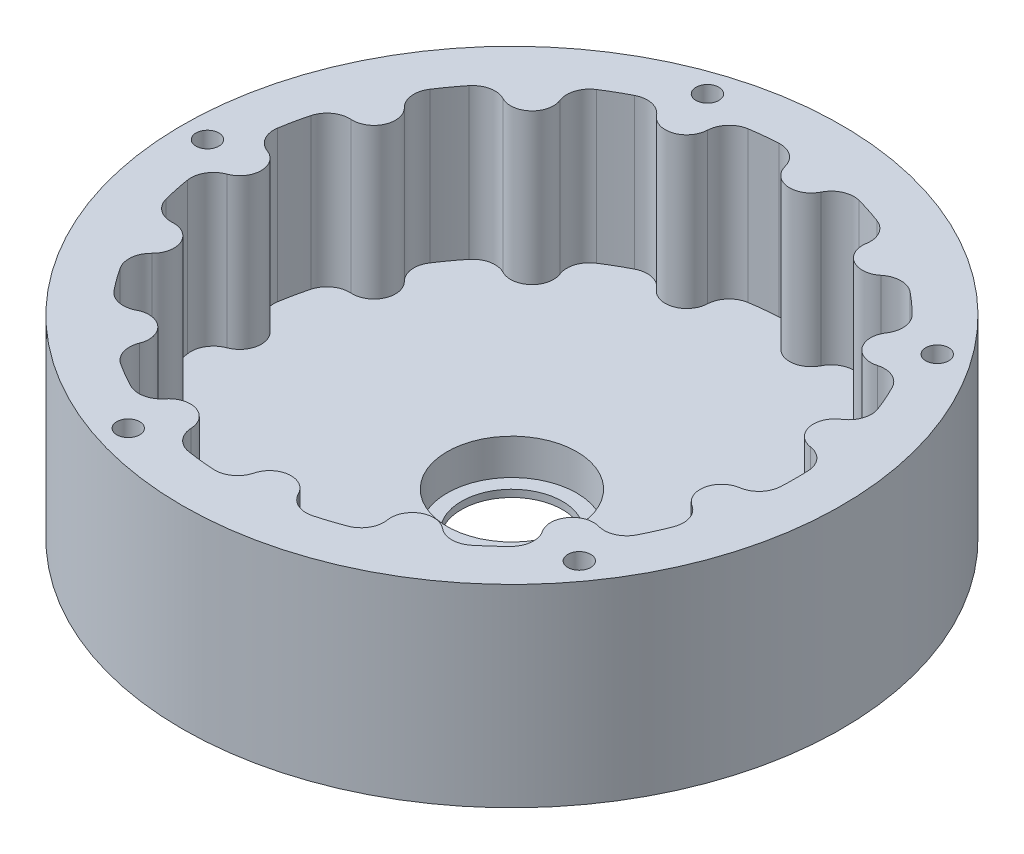
SolidWorks part; units mm, degrees
ref_plane "Front Plane" through (0, 0, 0) normal (0, 0, 1) x (1, 0, 0)
ref_plane "Top Plane" through (0, 0, 0) normal (0, 1, 0) x (1, 0, 0)
ref_plane "Right Plane" through (0, 0, 0) normal (1, 0, 0) x (0, 0, -1)
sketch "Sketch1" plane through (0, 0, 0) normal (0, 1, 0) x (1, 0, 0)
  line L0 (0, 0) -> (-38, 0) construction
  line L1 (-38.6368, 8.2125) -> (0, 0) construction
  circle A0 centre (0, 0) radius 46
  arc A1 (-36.9604, -2.8141) -> (-36.9604, 2.8141) centre (-38, 0) ccw
  arc A2 (-36.9604, 2.8141) -> (-38.9946, 6.2987) centre (-35.8602, 5.7924) cw
  arc A3 (-38.9946, 6.2987) -> (-38.6368, 8.2125) centre (0, 0) cw
  arc A4 (-38.9946, -6.2987) -> (-38.6368, -8.2125) centre (0, 0) ccw
  arc A5 (-36.9604, -2.8141) -> (-38.9946, -6.2987) centre (-35.8602, -5.7924) ccw
  arc A6 (-38.1852, 10.1064) -> (-38.6368, 8.2125) centre (0, 0) ccw
  arc A7 (-34.9096, 12.4623) -> (-38.1852, 10.1064) centre (-35.1159, 9.294) ccw
  arc A8 (-34.9096, 12.4623) -> (-32.6204, 17.604) centre (-34.7147, 15.456) ccw
  arc A9 (-32.6204, 17.604) -> (-33.0614, 21.6147) centre (-30.4039, 19.8773) cw
  arc A10 (-33.0614, 21.6147) -> (-31.9562, 23.2175) centre (0, 0) cw
  arc A11 (-30.7733, 24.764) -> (-31.9562, 23.2175) centre (0, 0) ccw
  arc A12 (-26.8226, 25.5839) -> (-30.7733, 24.764) centre (-28.2997, 22.7734) ccw
  arc A13 (-26.8226, 25.5839) -> (-22.64, 29.35) centre (-25.427, 28.2395) ccw
  arc A14 (-22.64, 29.35) -> (-21.4116, 33.1933) centre (-19.6906, 30.5252) cw
  arc A15 (-21.4116, 33.1933) -> (-19.75, 34.208) centre (0, 0) cw
  arc A16 (-18.0404, 35.1396) -> (-19.75, 34.208) centre (0, 0) ccw
  arc A17 (-14.0978, 34.2818) -> (-18.0404, 35.1396) centre (-16.5903, 32.3151) ccw
  arc A18 (-14.0978, 34.2818) -> (-8.745, 36.0211) centre (-11.7426, 36.1401) ccw
  arc A19 (-8.745, 36.0211) -> (-6.0596, 39.0324) centre (-5.5725, 35.895) cw
  arc A20 (-6.0596, 39.0324) -> (-4.1289, 39.2836) centre (0, 0) cw
  arc A21 (-2.1881, 39.4393) -> (-4.1289, 39.2836) centre (0, 0) ccw
  arc A22 (1.0647, 37.0521) -> (-2.1881, 39.4393) centre (-2.0123, 36.2692) ccw
  arc A23 (1.0647, 37.0521) -> (6.6621, 36.4638) centre (3.9721, 37.7918) ccw
  arc A24 (6.6621, 36.4638) -> (10.3402, 38.1226) centre (9.5091, 35.0583) cw
  arc A25 (10.3402, 38.1226) -> (12.2062, 37.5667) centre (0, 0) cw
  arc A26 (14.0425, 36.9196) -> (12.2062, 37.5667) centre (0, 0) ccw
  arc A27 (16.0431, 33.4157) -> (14.0425, 36.9196) centre (12.9137, 33.952) ccw
  arc A28 (16.0431, 33.4157) -> (20.9173, 30.6016) centre (19, 32.909) ccw
  arc A29 (20.9173, 30.6016) -> (24.9521, 30.6209) centre (22.9465, 28.1596) cw
  arc A30 (24.9521, 30.6209) -> (26.4307, 29.3542) centre (0, 0) cw
  arc A31 (27.845, 28.0162) -> (26.4307, 29.3542) centre (0, 0) ccw
  arc A32 (28.2475, 24.0015) -> (27.845, 28.0162) centre (25.6068, 25.7642) ccw
  arc A33 (28.2475, 24.0015) -> (31.5557, 19.4481) centre (30.7426, 22.3358) ccw
  arc A34 (31.5557, 19.4481) -> (35.2495, 17.8247) centre (32.4162, 16.3919) cw
  arc A35 (35.2495, 17.8247) -> (36.085, 16.0661) centre (0, 0) cw
  arc A36 (36.8329, 14.2685) -> (36.085, 16.0661) centre (0, 0) ccw
  arc A37 (35.5677, 10.4371) -> (36.8329, 14.2685) centre (33.8723, 13.1216) ccw
  arc A38 (35.5677, 10.4371) -> (36.7378, 4.9319) centre (37.1696, 7.9006) ccw
  arc A39 (36.7378, 4.9319) -> (39.452, 1.9464) centre (36.2809, 1.7899) cw
  arc A40 (39.452, 1.9464) -> (39.5, 0) centre (0, 0) cw
  arc A41 (39.452, -1.9464) -> (39.5, 0) centre (0, 0) ccw
  arc A42 (36.7378, -4.9319) -> (39.452, -1.9464) centre (36.2809, -1.7899) ccw
  arc A43 (36.7378, -4.9319) -> (35.5677, -10.4371) centre (37.1696, -7.9006) ccw
  arc A44 (35.5677, -10.4371) -> (36.8329, -14.2685) centre (33.8723, -13.1216) cw
  arc A45 (36.8329, -14.2685) -> (36.085, -16.0661) centre (0, 0) cw
  arc A46 (35.2495, -17.8247) -> (36.085, -16.0661) centre (0, 0) ccw
  arc A47 (31.5557, -19.4481) -> (35.2495, -17.8247) centre (32.4162, -16.3919) ccw
  arc A48 (31.5557, -19.4481) -> (28.2475, -24.0015) centre (30.7426, -22.3358) ccw
  arc A49 (28.2475, -24.0015) -> (27.845, -28.0162) centre (25.6068, -25.7642) cw
  arc A50 (27.845, -28.0162) -> (26.4307, -29.3542) centre (0, 0) cw
  arc A51 (24.9521, -30.6209) -> (26.4307, -29.3542) centre (0, 0) ccw
  arc A52 (20.9173, -30.6016) -> (24.9521, -30.6209) centre (22.9465, -28.1596) ccw
  arc A53 (20.9173, -30.6016) -> (16.0431, -33.4157) centre (19, -32.909) ccw
  arc A54 (16.0431, -33.4157) -> (14.0425, -36.9196) centre (12.9137, -33.952) cw
  arc A55 (14.0425, -36.9196) -> (12.2062, -37.5667) centre (0, 0) cw
  arc A56 (10.3402, -38.1226) -> (12.2062, -37.5667) centre (0, 0) ccw
  arc A57 (6.6621, -36.4638) -> (10.3402, -38.1226) centre (9.5091, -35.0583) ccw
  arc A58 (6.6621, -36.4638) -> (1.0647, -37.0521) centre (3.9721, -37.7918) ccw
  arc A59 (1.0647, -37.0521) -> (-2.1881, -39.4393) centre (-2.0123, -36.2692) cw
  arc A60 (-2.1881, -39.4393) -> (-4.1289, -39.2836) centre (0, 0) cw
  arc A61 (-6.0596, -39.0324) -> (-4.1289, -39.2836) centre (0, 0) ccw
  arc A62 (-8.745, -36.0211) -> (-6.0596, -39.0324) centre (-5.5725, -35.895) ccw
  arc A63 (-8.745, -36.0211) -> (-14.0978, -34.2818) centre (-11.7426, -36.1401) ccw
  arc A64 (-14.0978, -34.2818) -> (-18.0404, -35.1396) centre (-16.5903, -32.3151) cw
  arc A65 (-18.0404, -35.1396) -> (-19.75, -34.208) centre (0, 0) cw
  arc A66 (-21.4116, -33.1933) -> (-19.75, -34.208) centre (0, 0) ccw
  arc A67 (-22.64, -29.35) -> (-21.4116, -33.1933) centre (-19.6906, -30.5252) ccw
  arc A68 (-22.64, -29.35) -> (-26.8226, -25.5839) centre (-25.427, -28.2395) ccw
  arc A69 (-26.8226, -25.5839) -> (-30.7733, -24.764) centre (-28.2997, -22.7734) cw
  arc A70 (-30.7733, -24.764) -> (-31.9562, -23.2175) centre (0, 0) cw
  arc A71 (-33.0614, -21.6147) -> (-31.9562, -23.2175) centre (0, 0) ccw
  arc A72 (-32.6204, -17.604) -> (-33.0614, -21.6147) centre (-30.4039, -19.8773) ccw
  arc A73 (-32.6204, -17.604) -> (-34.9096, -12.4623) centre (-34.7147, -15.456) ccw
  arc A74 (-34.9096, -12.4623) -> (-38.1852, -10.1064) centre (-35.1159, -9.294) cw
  arc A75 (-38.1852, -10.1064) -> (-38.6368, -8.2125) centre (0, 0) cw
  dimension "D1" = 92
  dimension "D3" = 3
  dimension "D4" = 39.5
  dimension "D5" = 3.175
  dimension "D2" = 38
  dimension "D6" = 12
  dimension "D7" = 15
extrude "Boss-Extrude1" add sketch "Sketch1" along normal blind 27 contours A0 A74 A75 A4 A5 A1 A2 A3 A6 A7 A8 A9 A10 A11 A12 A13 A14 A15 A16 A17 A18 A19 A20 A21 A22 A23 A24 A25 A26 A27 A28 A29 A30 A31 A32 A33 A34 A35 A36 A37 A38 A39 A40 A41 A42 A43 A44 A45 A46 A47 region at (-44.6989, 0, 0)
extrude "Boss-Extrude2" add sketch "Sketch1<3>" along normal blind 6 contours A0 A74 A75 A4 A5 A1 A2 A3 A6 A7 A8 A9 A10 A11 A12 A13 A14 A15 A16 A17 A18 A19 A20 A21 A22 A23 A24 A25 A26 A27 A28 A29 A30 A31 A32 A33 A34 A35 A36 A37 A38 A39 A40 A41 A42 A43 A44 A45 A46 A47 | A75 A74 A73 A72 A71 A70 A69 A68 A67 A66 A65 A64 A63 A62 A61 A60 A59 A58 A57 A56 A55 A54 A53 A52 A51 A50 A49 A48 A47 A46 A45 A44 A43 A42 A41 A40 A39 A38 A37 A36 A35 A34 A33 A32 A31 A30 A29 A28 A27 A26 A25 region at (-44.6989, 0, 0) region at (0, 0, 0)
sketch "Sketch1<3>" plane through (0, 0, 0) normal (0, 1, 0) x (1, 0, 0) same geometry as "Sketch1"
sketch "Sketch2" plane through (0, 0, 0) normal (0, 1, 0) x (1, 0, 0)
  circle A0 centre (0, 0) radius 9.05
  circle A1 centre (0, 0) radius 7.05
  dimension "D1" = 18.1
extrude "Cut-Extrude1" cut sketch "Sketch2" along normal through all contours A1 region at (0, 0, 0)
extrude "Cut-Extrude2" cut sketch "Sketch2<3>" along normal through all from offset 1 contours A0 A1 region at (-8.794, 0, 0)
sketch "Sketch2<3>" plane through (0, 0, 0) normal (0, 1, 0) x (1, 0, 0) same geometry as "Sketch2"
hole_wizard "M3 Clearance Hole1" positions "Sketch4" profile "Sketch6" hole size "M3" standard "ANSI Metric" end condition through all
sketch "Sketch4" plane through (0, 27, 0) normal (0, 1, 0) x (1, 0, 0)
  line L2 (-42.5, 0) -> (0, 0) construction
  point P10 (-42.5, 0)
  dimension "D1" = 42.5
sketch "Sketch6" plane through (-42.5, 27, 0) normal (1, 0, 0) x (0, 0, 1)
  line L0 (0, 0) -> (0, 27)
  line L1 (0, 27) -> (1.6, 27)
  line L2 (1.6, 27) -> (1.6, 0)
  line L5 (1.6, 0) -> (0, 0)
  line L11 (0, -6.35) -> (0, 107.95) construction
  dimension "Thru Hole Dia." = 3.2
  dimension "Thru Hole Depth" = 27
pattern_circular "CirPattern1" count 5 over 360 about axis through (0, 27, 0) along (0, -1, 0) of "M3 Clearance Hole1" reverse direction yes
equation "\"Ratio\"= 15"
equation "\"Hull Diameter\"= 92"
equation "\"Fixed Ring Diameter\"= 76"
equation "\"Fixed Pin Diameter\"= 6"
equation "\"Output Ring Diameter\"= 40"
equation "\"Output Pin Diameter\"= 6"
equation "\"Disk Bearing Inner Diameter\"= 9"
equation "\"Disk Bearing Outer Diameter\"= 17"
equation "\"Disk Bearing Height\"= 5"
equation "\"Shaft Bearing Inner Diameter\"= 15"
equation "\"Shaft Bearing Outer Diameter\"= 21"
equation "\"Shaft Bearing Height\"= 4"
equation "\"Eccentricity\"= 1.5"
equation "\"Disk Height\"= 8"
equation "\"Disk Spacing\"= 5"
equation "\"Hull Height\"= 40"
equation "\"Shaft End Bearing Inner Diameter\"= 12"
equation "\"Shaft End Bearing Outer Diameter\"= 18"
equation "\"Shaft End Bearing Height\"= 4"
equation "\"Output Bearing Inner Diameter\"= 55"
equation "\"Output Bearing Outer Diameter\"= 72"
equation "\"Outer Bearing Height\"= 9"
equation "\"D1@Sketch1\"=\"Hull Diameter\""
equation "\"D3@Sketch1\"=\"Fixed Pin Diameter\"/2"
equation "\"D2@Sketch1\"=\"Fixed Ring Diameter\"/2"
equation "\"D4@Sketch1\"=(\"Fixed Ring Diameter\"/2)+(\"Eccentricity\")"
equation "\"D6@Sketch1\"=180/(\"Ratio\")"
equation "\"D7@Sketch1\"=\"Ratio\""
equation "\"D1@Sketch2\"=\"Shaft End Bearing Outer Diameter\"+0.1"
